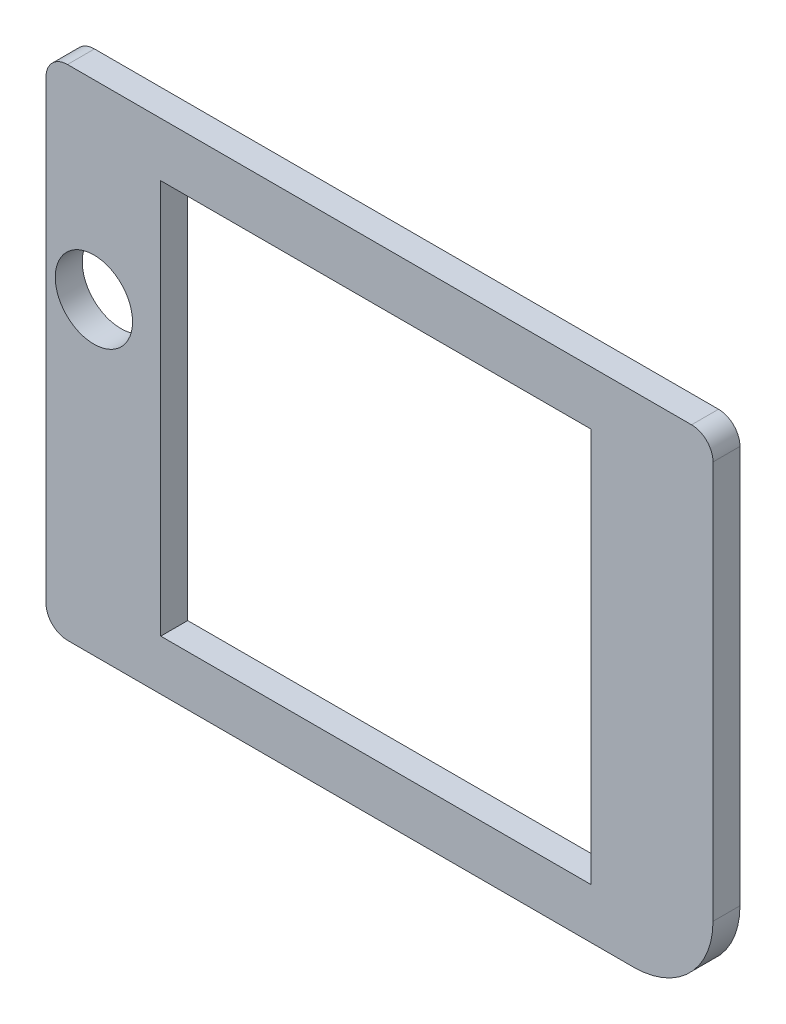
SolidWorks part; units mm, degrees
ref_plane "Front Plane" through (0, 0, 0) normal (0, 0, 1) x (1, 0, 0)
ref_plane "Top Plane" through (0, 0, 0) normal (0, 1, 0) x (1, 0, 0)
ref_plane "Right Plane" through (0, 0, 0) normal (1, 0, 0) x (0, 0, -1)
sketch "Sketch1" plane through (0, 0, 0) normal (0, 0, 1) x (1, 0, 0)
  line L1 (-26.2308, 73.6471) -> (38.6518, 73.6471)
  line L3 (-44.6471, -70.649) -> (-44.6471, 70.649)
  line L5 (27.0934, -73.6471) -> (-41.649, -73.6471)
  line L7 (-24.0867, 73.6955) -> (-35.6911, 73.6955)
  line L15 (-16.3293, -29.1587) -> (-16.3293, -23.8757)
  line L19 (44.6471, 67.6705) -> (44.6471, -53.896)
  line L20 (-0.4012, -48.3225) -> (6.5714, -44.4005)
  line L21 (8.2266, -47.343) -> (1.254, -51.2651)
  line L22 (-44.6471, 73.6471) -> (44.6471, 73.6471)
  line L23 (44.6471, 73.6471) -> (44.6471, -73.6471)
  line L24 (44.6471, -73.6471) -> (-44.6471, -73.6471)
  line L25 (-44.6471, -73.6471) -> (-44.6471, 73.6471)
  line L26 (-25.1679, 56.2163) -> (-25.1679, 10.288)
  line L27 (-25.1679, 10.288) -> (24.9222, 10.288)
  line L28 (24.9222, 10.288) -> (24.9222, 56.2163)
  line L29 (24.9222, 56.2163) -> (-25.1679, 56.2163)
  line L34 (36.6393, 62.5051) -> (-36.0272, 62.5051)
  line L35 (-38.5272, 60.0051) -> (-38.5272, 6.9331)
  line L36 (-36.0272, 4.4331) -> (29.8893, 4.4331)
  line L37 (39.1393, 13.6831) -> (39.1393, 60.0051)
  line L38 (-16.4012, -48.3225) -> (-9.4286, -44.4005)
  line L39 (-7.7734, -47.343) -> (-14.746, -51.2651)
  line L41 (44.6471, 70.649) -> (44.6471, 67.6705)
  line L43 (38.6518, 73.6471) -> (41.649, 73.6471)
  line L45 (-41.649, 73.6471) -> (-26.2308, 73.6471)
  line L150 (42.2525, -55.0539) -> (42.2511, -54.9499)
  circle A0 centre (34.1495, 24.0914) radius 10.7
  circle A2 centre (-26.9008, -26.5172) radius 3.6
  arc A3 (8.2266, -47.343) -> (6.5714, -44.4005) centre (7.399, -45.8717) ccw
  arc A6 (-16.4012, -48.3225) -> (-14.746, -51.2651) centre (-15.5736, -49.7938) ccw
  arc A7 (-7.7734, -47.343) -> (-9.4286, -44.4005) centre (-8.601, -45.8717) ccw
  circle A15 centre (18.8495, -29.5462) radius 3.5
  circle A16 centre (32.9602, -21.4767) radius 3.5
  arc A17 (-0.4012, -48.3225) -> (1.254, -51.2651) centre (0.4264, -49.7938) ccw
  circle A19 centre (-32.9539, 40.3411) radius 4.5
  arc A24 (39.1393, 60.0051) -> (36.6393, 62.5051) centre (36.6393, 60.0051) ccw
  arc A25 (-36.0272, 62.5051) -> (-38.5272, 60.0051) centre (-36.0272, 60.0051) ccw
  arc A26 (-38.5272, 6.9331) -> (-36.0272, 4.4331) centre (-36.0272, 6.9331) ccw
  arc A27 (29.8893, 4.4331) -> (39.1393, 13.6831) centre (29.8893, 13.6831) ccw
  ellipse E3 centre (-41.649, -70.649) end of major axis (-39.5276, -72.7703) minor radius 2.9963 (-44.6471, -70.649) -> (-41.649, -73.6471) ccw
  ellipse E5 centre (41.649, 70.649) end of major axis (39.5276, 72.7703) minor radius 2.9963 (44.6471, 70.649) -> (41.649, 73.6471) ccw
  ellipse E7 centre (-41.649, 70.649) end of major axis (-43.7703, 68.5276) minor radius 2.9963 (-41.649, 73.6471) -> (-44.6471, 70.649) ccw
  spline S1 degree 3 poles (44.6485, -54) (44.663, -55.258) (44.5568, -56.5068) (44.2157, -58.3662) (44.0715, -58.9837) (43.7192, -60.2138) (43.5128, -60.8202) (42.8075, -62.6008) (42.2221, -63.7422) (41.3373, -65.1085) (41.1525, -65.3788) (40.7717, -65.907) (40.5751, -66.1657) (39.9672, -66.9256) (39.1083, -67.8961) (38.1523, -68.7812) (37.1464, -69.6222) (36.6152, -70.0225) (34.9811, -71.1285) (33.8311, -71.748) (32.3187, -72.3766) (32.0124, -72.495) (31.3922, -72.7168) (31.0776, -72.8204) (30.1333, -73.105) (29.5001, -73.2613) (27.5898, -73.6337) (26.302, -73.7542) (25, -73.7456) knots 0 0 0 0 0.125 0.125 0.1875 0.1875 0.25 0.25 0.375 0.375 0.40625 0.40625 0.4375 0.4375 0.5 0.5625 0.5625 0.625 0.625 0.75 0.75 0.78125 0.78125 0.8125 0.8125 0.875 0.875 1 1 1 1
  dimension "D4" = 21.4
  dimension "D8" = 7
  dimension "D11" = 9
  dimension "D12" = 7.2
  dimension "D1" = 10.4977
  dimension "D2" = 89.2943
  dimension "D3" = 147.2943
  dimension "D5" = 25.9097
  dimension "D6" = 8.0696
  dimension "D7" = 14.1107
  dimension "D9" = 7.7861
  dimension "D10" = 22.1641
  dimension "D13" = 10.5715
extrude "Boss-Extrude2" add sketch "Sketch1" along normal blind 3.14 separate body contours L36 A27 L37 A0 L28 L27 L26 L29 A24 L34 A25 L35 A26 A19 | L37 A0 L28 region at (30.9538, 35.3151, 0) region at (32.4596, 24.0914, 0)
